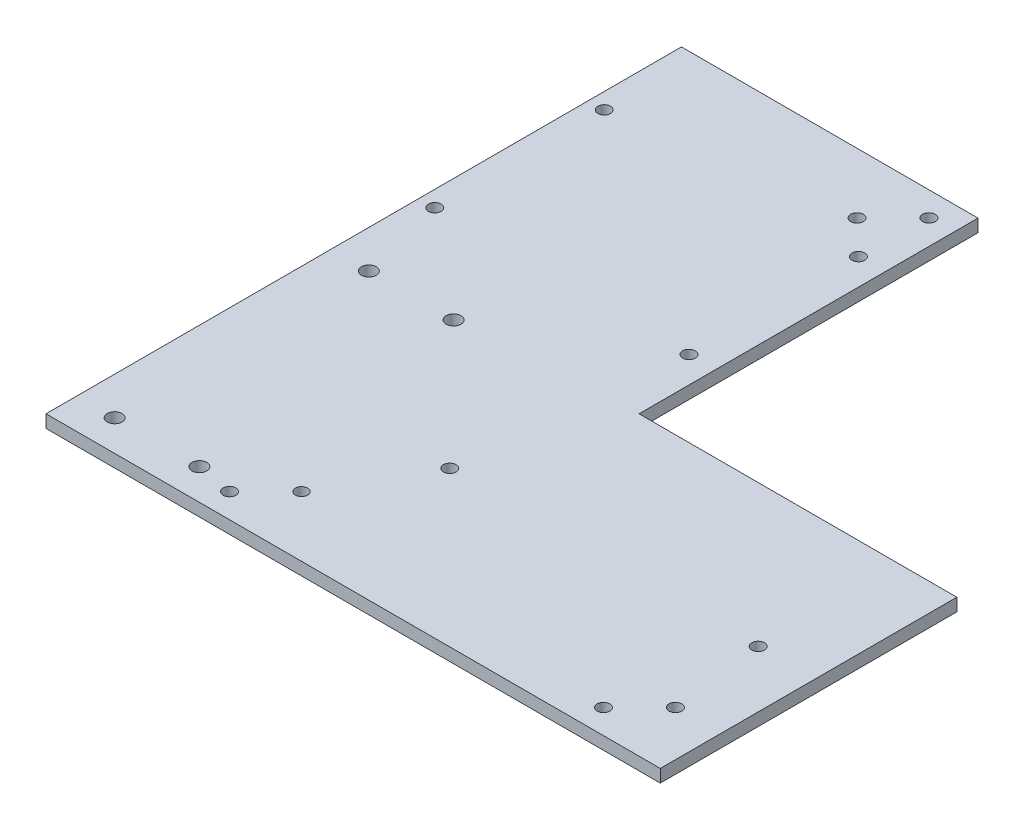
SolidWorks part; units mm, degrees
ref_plane "Front Plane" through (0, 0, 0) normal (0, 0, 1) x (1, 0, 0)
ref_plane "Top Plane" through (0, 0, 0) normal (0, 1, 0) x (1, 0, 0)
ref_plane "Right Plane" through (0, 0, 0) normal (1, 0, 0) x (0, 0, -1)
sketch "Sketch1" plane through (0, 0, 0) normal (0, 1, 0) x (1, 0, 0)
  line L0 (-72.5, -35) -> (72.5, -35)
  line L2 (-72.5, -35) -> (-72.5, 35)
  line L4 (72.5, -35) -> (72.5, 35)
  line L5 (-72.5, -35) -> (72.5, 35) construction
  line L6 (-72.5, 35) -> (72.5, -35) construction
  line L15 (-2.5, 35) -> (72.5, 35)
  line L17 (-72.5, 35) -> (-72.5, 115)
  line L18 (-72.5, 115) -> (-2.5, 115)
  line L19 (-2.5, 35) -> (-2.5, 115)
  circle A0 centre (-34.9264, -29.2426) radius 1.5
  circle A1 centre (-26.4411, -20.7574) radius 1.4446
  circle A2 centre (53.3381, -29.2426) radius 1.5
  circle A3 centre (61.8234, -20.7574) radius 1.5
  circle A4 centre (-16.8144, 100.7574) radius 1.5
  circle A5 centre (-8.3291, 109.2426) radius 1.5
  circle A6 centre (-13.6998, 1.5) radius 1.5
  circle A7 centre (59.1092, 1.5) radius 1.5
  circle A8 centre (-63.5846, -27.7106) radius 1.75
  circle A9 centre (-43.5846, -27.7106) radius 1.75
  circle A10 centre (-43.5846, 32.2894) radius 1.75
  circle A11 centre (-63.5846, 32.2894) radius 1.75
  circle A12 centre (-68.7404, 53.0097) radius 1.5
  circle A13 centre (-68.7404, 93.0097) radius 1.5
  circle A14 centre (-8.7404, 93.0097) radius 1.5
  circle A15 centre (-8.7404, 53.0097) radius 1.5
  point P0 (0, 0)
  dimension "D1" = 145
  dimension "D2" = 70
  dimension "D3" = 70
  dimension "D4" = 150
extrude "Boss-Extrude1" add sketch "Sketch1" along normal blind 3
